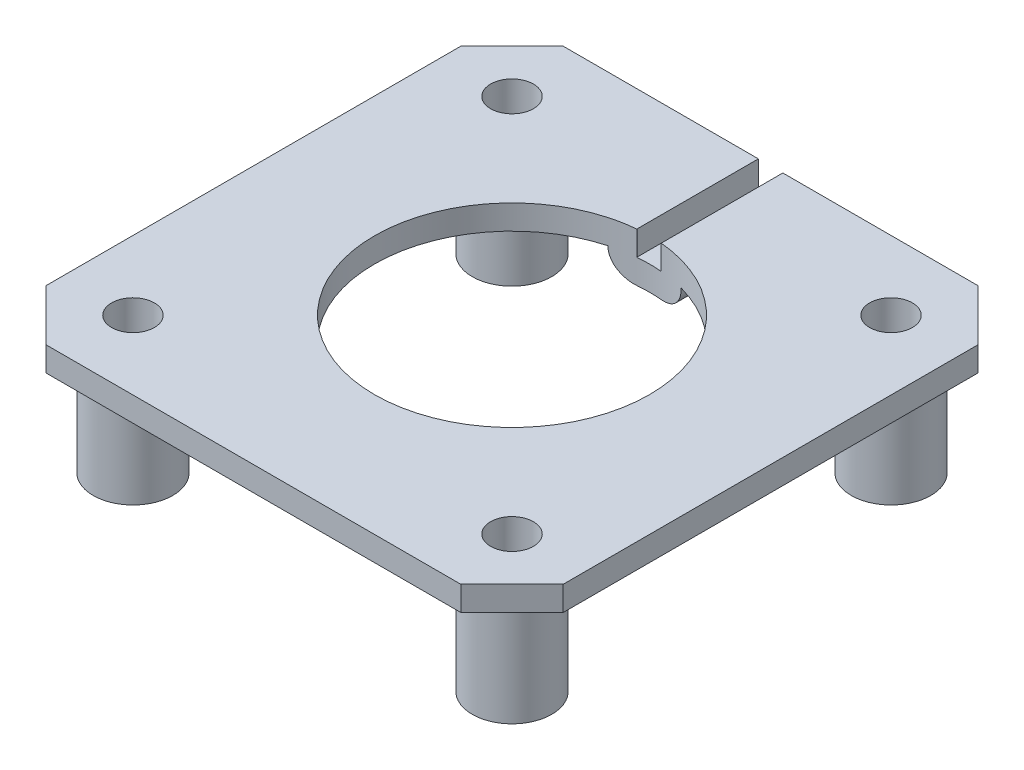
SolidWorks part; units mm, degrees
ref_plane "Front Plane" through (0, 0, 0) normal (0, 0, 1) x (1, 0, 0)
ref_plane "Top Plane" through (0, 0, 0) normal (0, 1, 0) x (1, 0, 0)
ref_plane "Right Plane" through (0, 0, 0) normal (1, 0, 0) x (0, 0, -1)
sketch "Sketch1" plane through (0, 0, 0) normal (0, 1, 0) x (1, 0, 0)
  circle A4 centre (-15.5, 15.5) radius 3.25
  dimension "D3" = 6.5
  dimension "D1" = 15.5
  dimension "D2" = 15.5
extrude "Boss-Extrude1" add sketch "Sketch1" along normal blind 11.15
mirror "Mirror2" about plane through (0, 0, 0) normal (1, 0, 0) of bodies 101
mirror "Mirror3" about plane through (0, 0, 0) normal (0, 0, 1) of bodies 101 102
sketch "Sketch2" plane through (0, 11.15, 0) normal (0, 1, 0) x (1, 0, 0)
  line L1 (-21.15, 21.15) -> (21.15, 21.15)
  line L2 (-21.15, 21.15) -> (-21.15, -21.15)
  line L3 (-21.15, -21.15) -> (21.15, -21.15)
  line L4 (21.15, 21.15) -> (21.15, -21.15)
  line L5 (-21.15, 21.15) -> (21.15, -21.15) construction
  line L6 (-21.15, -21.15) -> (21.15, 21.15) construction
  circle A0 centre (0, 0) radius 11.25
  dimension "D1" = 22.5
  dimension "D4" = 42.3
extrude "Boss-Extrude2" add sketch "Sketch2" against normal blind 2
sketch "Sketch3" plane through (0, 11.15, 0) normal (0, 1, 0) x (1, 0, 0)
  line L0 (-16.9631, 21.15) -> (-21.15, 16.9631)
  line L1 (21.15, 21.15) -> (-21.15, 21.15) construction
  line L2 (-21.15, 21.15) -> (-21.15, -21.15) construction
  line L3 (16.9631, -21.15) -> (21.15, -16.9631)
  line L4 (-21.15, -21.15) -> (21.15, -21.15) construction
  line L5 (21.15, -21.15) -> (21.15, 21.15) construction
  line L6 (-21.15, 16.9631) -> (-21.15, 21.15)
  line L7 (-21.15, 21.15) -> (-16.9631, 21.15)
  line L8 (21.15, -16.9631) -> (21.15, -21.15)
  line L9 (21.15, -21.15) -> (16.9631, -21.15)
  dimension "D1" = 45
  dimension "D2" = 53.9
extrude "Cut-Extrude1" cut sketch "Sketch3" against normal through all
mirror "Mirror4" about plane through (0, 0, 0) normal (0, 0, 1) of "Cut-Extrude1"
sketch "Sketch4" plane through (0, 0, 0) normal (0, -1, 0) x (1, 0, 0)
  circle A1 centre (15.5, -15.5) radius 3.25 construction
  circle A3 centre (15.5, -15.5) radius 1.75
  dimension "D1" = 3.5
extrude "Cut-Extrude2" cut sketch "Sketch4" against normal through all
mirror "Mirror5" about plane through (0, 0, 0) normal (1, 0, 0) of "Cut-Extrude2"
mirror "Mirror6" about plane through (0, 0, 0) normal (0, 0, 1) of "Mirror5"
sketch "Sketch6" plane through (0, 9.15, 0) normal (0, -1, 0) x (1, 0, 0)
  line L0 (0, -21.15) -> (0, -11.25) construction
  line L1 (16.9631, -21.15) -> (-16.9631, -21.15) construction
  line L2 (-3, -21.15) -> (-3, -10.8426)
  line L3 (3, -21.15) -> (3, -10.8426)
  line L4 (3, -21.15) -> (-3, -21.15)
  circle A0 centre (0, 0) radius 11.25 construction
  arc A3 (-3, -10.8426) -> (3, -10.8426) centre (0, 0) ccw
  point P7 (0, -18.325)
  dimension "D1" = 6
  dimension "D2" = 3
extrude "Boss-Extrude3" add sketch "Sketch6" along normal blind 2
sketch "Sketch7" plane through (0, 11.15, 0) normal (0, 1, 0) x (1, 0, 0)
  line L0 (0, 11.25) -> (0, 21.15) construction
  line L1 (16.9631, 21.15) -> (-16.9631, 21.15) construction
  line L2 (-1, 11.25) -> (-1, 21.15)
  line L3 (1, 11.25) -> (1, 21.15)
  circle A0 centre (0, 0) radius 11.25 construction
  arc A1 (-1, 11.25) -> (1, 11.25) centre (0, 11.25) ccw
  arc A2 (1, 21.15) -> (-1, 21.15) centre (0, 21.15) ccw
  point P6 (0, 16.2)
  dimension "D1" = 2
extrude "Cut-Extrude3" cut sketch "Sketch7" against normal blind 2
fillet "Fillet1" radius 2 2 edges at (3, 7.15, -15.9963) (-3, 7.15, -15.9963)
